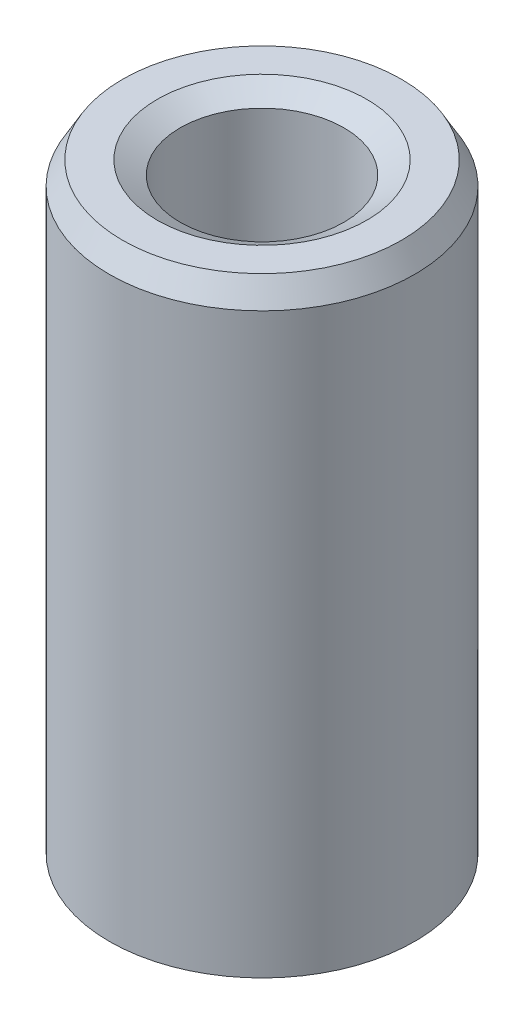
SolidWorks part; units mm, degrees
ref_plane "Front Plane" through (0, 0, 0) normal (0, 0, 1) x (1, 0, 0)
ref_plane "Top Plane" through (0, 0, 0) normal (0, 1, 0) x (1, 0, 0)
ref_plane "Right Plane" through (0, 0, 0) normal (1, 0, 0) x (0, 0, -1)
sketch "Sketch1" plane through (0, 0, 0) normal (0, 1, 0) x (1, 0, 0)
  circle A0 centre (0, 0) radius 15
  dimension "SLEEVE_OD" = 30
extrude "Boss-Extrude1" add sketch "Sketch1" along normal blind 60.2965
sketch "Sketch2" plane through (0, 0, 0) normal (0, 1, 0) x (1, 0, 0)
  circle A0 centre (0, 0) radius 8.0444
  dimension "BORE_D" = 16.0888
extrude "Cut-Extrude1" cut sketch "Sketch2" along normal through all
chamfer "Chamfer1" distance 2.2489 angle 30 4 edges at (0, 60.2965, 8.0444) (0, 0, 8.0444) (0, 0, 15) (0, 60.2965, 15) first distance on face at (0, 60.2965, 8.0444) first distance on face at (0, 0, 8.0444) first distance on face at (0, 60.2965, 15)
